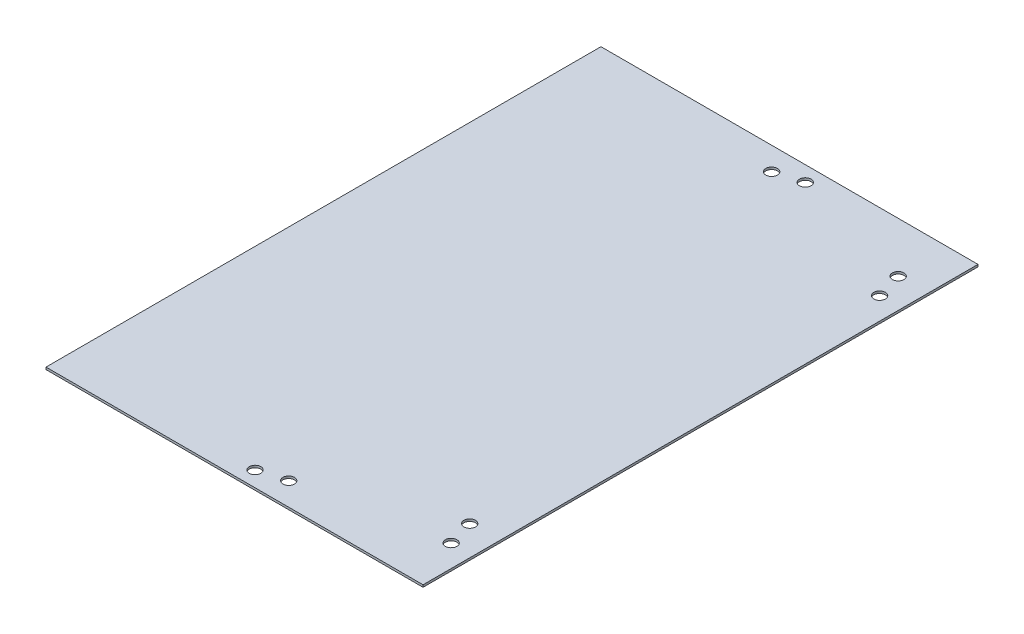
SolidWorks part; units mm, degrees
material "Alumina"
ref_plane "Front Plane" through (0, 0, 0) normal (0, 0, 1) x (1, 0, 0)
ref_plane "Top Plane" through (0, 0, 0) normal (0, 1, 0) x (1, 0, 0)
ref_plane "Right Plane" through (0, 0, 0) normal (1, 0, 0) x (0, 0, -1)
sketch "Sketch3" plane through (0, 0, 0) normal (0, 1, 0) x (1, 0, 0)
  line L1 (-110, 161.9) -> (110, 161.9)
  line L2 (-110, 161.9) -> (-110, -161.9)
  line L3 (-110, -161.9) -> (110, -161.9)
  line L4 (110, 161.9) -> (110, -161.9)
  line L5 (-110, 161.9) -> (110, -161.9) construction
  line L6 (-110, -161.9) -> (110, 161.9) construction
  point P0 (0, 0)
  dimension "D1" = 323.8
  dimension "D2" = 220
extrude "Boss-Extrude1" add sketch "Sketch3" along normal blind 1.2954
sketch "Sketch4" plane through (0, 1.2954, 0) normal (0, 1, 0) x (1, 0, 0)
  circle A0 centre (97.1046, -132.62) radius 3.3782
  circle A1 centre (92.7046, -117.38) radius 3.3782
  circle A2 centre (18.2246, -148.5) radius 3.3782
  circle A3 centre (2.9846, -152.9) radius 3.3782
  circle A4 centre (97.1046, 117.38) radius 3.3782
  circle A6 centre (92.7046, 132.62) radius 3.3782
  circle A7 centre (18.2246, 152.9) radius 3.3782
  circle A8 centre (2.9846, 148.5) radius 3.3782
extrude "Cut-Extrude1" cut sketch "Sketch4" against normal up to next
